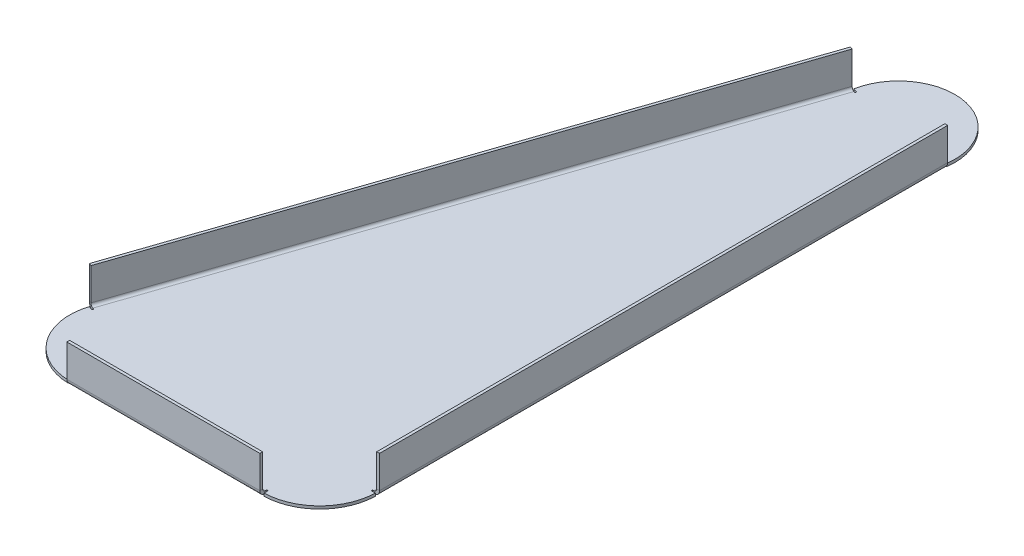
SolidWorks part; units mm, degrees
note: The reader was unsure of these and kept them because the rebuilt part matched: flange length of "Edge-Flange1", "Edge-Flange2", "Edge-Flange3".
ref_plane "Front Plane" through (0, 0, 0) normal (0, 0, 1) x (1, 0, 0)
ref_plane "Top Plane" through (0, 0, 0) normal (0, 1, 0) x (1, 0, 0)
ref_plane "Right Plane" through (0, 0, 0) normal (1, 0, 0) x (0, 0, -1)
sketch "Sketch1" plane through (0, 0, 0) normal (0, 1, 0) x (1, 0, 0)
  line L3 (40.5414, 75) -> (40.5414, -75)
  line L10 (11.2125, 79.8454) -> (-39.7409, -70.1546)
  line L11 (-25.4767, -90.0647) -> (25.4767, -90.0647)
  arc A0 (11.2125, 79.8454) -> (40.5414, 75) centre (25.8769, 77.4227) cw
  arc A1 (25.4767, -90.0647) -> (40.5414, -75) centre (25.4767, -75) ccw
  arc A3 (-39.7409, -70.1546) -> (-25.4767, -90.0647) centre (-25.4767, -75) ccw
  point P0 (0, 0)
  point P3 (25.4767, 0)
  point P11 (0, 0)
base flange "Base-Flange1" sketch "Sketch1" thickness 0.7366 reverse thickness direction no parameters "D1"=0.7366
edge flange "Edge-Flange1" sketch "Sketch8" flange angle 90 flange length 10 flange position material outside bend radius 0.7366 thickness 0.7366 relief rectangular parameters "D6"=10
sketch "Sketch8" plane through (40.5414, 0, 0) normal (1, 0, 0) x (0, 0, -1)
  line L2 (-75, 0) -> (-75, 9.2634)
  line L3 (-75, 9.2634) -> (75, 9.2634)
  line L4 (75, 9.2634) -> (75, 0)
  line L5 (-75, 0) -> (75, 0) construction
  line L6 (-75, 0) -> (75, 0)
bend "EdgeBend1" bend radius 0.7366 bend angle 90 parameters "D5"=1
edge flange "Edge-Flange2" sketch "Sketch13" flange angle 90 flange length 10 flange position material outside bend radius 0.7366 thickness 0.7366 relief rectangular parameters "D6"=10
sketch "Sketch13" plane through (0, 0, 90.0647) normal (0, 0, 1) x (1, 0, 0)
  line L0 (-25.4767, 0) -> (25.4767, 0) construction
  line L1 (-25.4767, 0) -> (25.4767, 0)
  line L2 (-25.4767, 0) -> (-25.4767, 9.2634)
  line L3 (-25.4767, 9.2634) -> (25.4767, 9.2634)
  line L4 (25.4767, 9.2634) -> (25.4767, 0)
bend "EdgeBend2" bend radius 0.7366 bend angle 90 parameters "D5"=2
edge flange "Edge-Flange3" sketch "Sketch16" flange angle 90 flange length 10 flange position material outside bend radius 0.7366 thickness 0.7366 relief rectangular parameters "D6"=10
sketch "Sketch16" plane through (-14.2642, 0, -4.8454) normal (-0.9469, 0, -0.3216) x (-0.3216, 0, 0.9469)
  line L0 (-79.209, 0) -> (79.209, 0) construction
  line L1 (-79.209, 0) -> (79.209, 0)
  line L2 (-79.209, 0) -> (-79.209, 9.2634)
  line L3 (-79.209, 9.2634) -> (79.209, 9.2634)
  line L4 (79.209, 9.2634) -> (79.209, 0)
bend "EdgeBend3" bend radius 0.7366 bend angle 90 parameters "D5"=3
sketch "Bend-Lines1" plane through (0, 0, 0) normal (0, 1, 0) x (1, 0, 0)
sketch "Bounding-Box1" plane through (0, 0, 0) normal (0, 1, 0) x (1, 0, 0)
sheet metal parameters "Sheet-Metal1" thickness 0.7366 parameters "D1"=0.7366
flat pattern "Flat-Pattern1" [suppressed]
sketch "Bend-Lines2" plane through (0, 0, 0) normal (0, 1, 0) x (1, 0, 0)
sketch "Bounding-Box2" [suppressed] plane through (0, 0, 0) normal (0, 1, 0) x (1, 0, 0)
sheet metal parameters "Sheet-Metal2" thickness 0.7366 parameters "D1"=0.7366
flat pattern "Flat-Pattern1" [suppressed]
sketch "Bend-Lines2" plane through (0, 0, 0) normal (0, 1, 0) x (1, 0, 0)
sketch "Bounding-Box2" [suppressed] plane through (0, 0, 0) normal (0, 1, 0) x (1, 0, 0)
bend of the flat pattern "Flatten-<EdgeBend1>1"
sheet metal parameters "Sheet-Metal3" thickness 0.7366 parameters "D1"=0.7366
flat pattern "Flat-Pattern1" [suppressed]
sketch "Bend-Lines2" plane through (0, 0, 0) normal (0, 1, 0) x (1, 0, 0)
sketch "Bounding-Box2" [suppressed] plane through (0, 0, 0) normal (0, 1, 0) x (1, 0, 0)
bend of the flat pattern "Flatten-<EdgeBend1>1"
bend of the flat pattern "Flatten-<EdgeBend2>1"
sheet metal parameters "Sheet-Metal4" thickness 0.7366 parameters "D1"=0.7366
flat pattern "Flat-Pattern1" [suppressed]
sketch "Bend-Lines2" plane through (0, 0, 0) normal (0, 1, 0) x (1, 0, 0)
sketch "Bounding-Box2" [suppressed] plane through (0, 0, 0) normal (0, 1, 0) x (1, 0, 0)
bend of the flat pattern "Flatten-<EdgeBend1>1"
bend of the flat pattern "Flatten-<EdgeBend2>1"
bend of the flat pattern "Flatten-<EdgeBend3>1"
